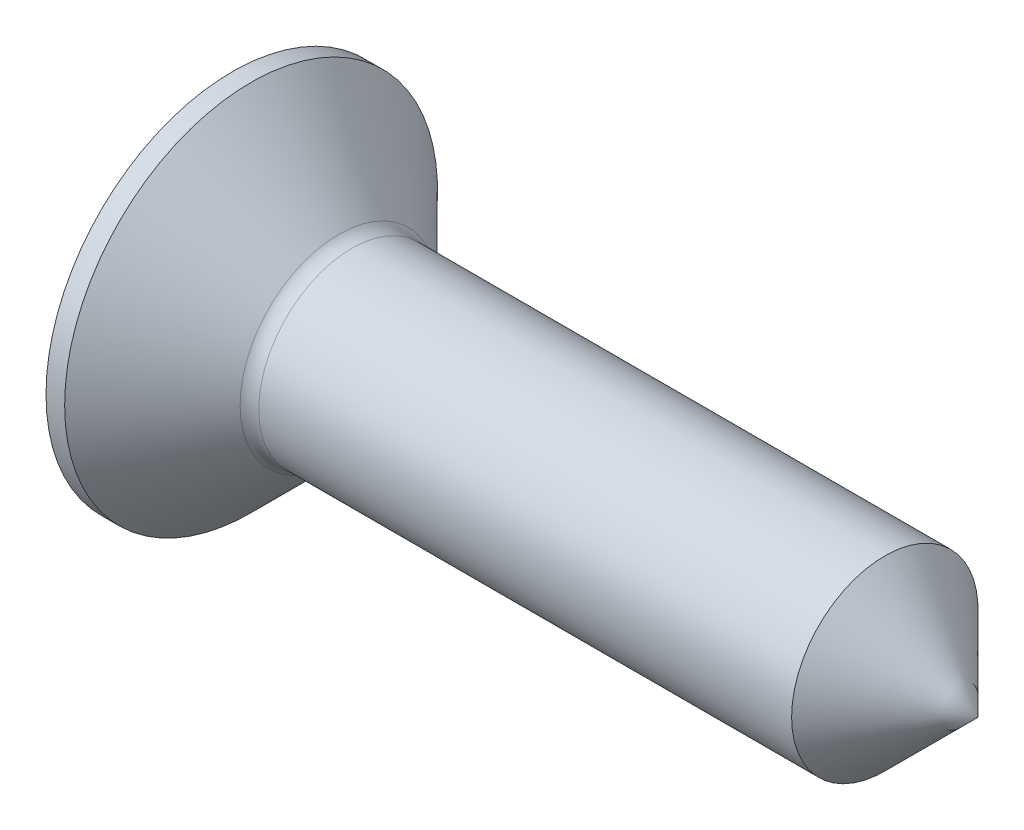
SolidWorks part; units mm, degrees
ref_plane "Front" through (0, 0, 0) normal (0, 0, 1) x (1, 0, 0)
ref_plane "Top" through (0, 0, 0) normal (0, 1, 0) x (1, 0, 0)
ref_plane "Right" through (0, 0, 0) normal (1, 0, 0) x (0, 0, -1)
sketch "Sketch1" plane through (0, 0, 0) normal (0, 1, 0) x (1, 0, 0)
  line L0 (-6.5065, 0) -> (5.6973, 0) construction
  line L1 (1.2, 1) -> (8, 1)
  line L2 (1.2, 1) -> (0.2, 2)
  line L3 (0.2, 2) -> (0, 2)
  line L4 (0, 2) -> (0, 0)
  line L5 (8, 1) -> (8, 0)
  line L6 (8, 0) -> (0, 0)
  dimension "D1" = 45
revolve "Base" add sketch "Sketch1" angle 360 about L0
cosmetic thread "ThreadCosmetic1" [suppressed] parameters "D1"=3, "D2"=1.5
sketch "Sketch3" plane through (0, 0, 0) normal (0, 0, 1) x (1, 0, 0)
  line L0 (4.8835, 0) -> (6.2249, 0) construction
  line L2 (8.1576, 0) -> (8.1576, 20)
  line L3 (8.1576, 20) -> (-12, 20)
  line L4 (-12, 20) -> (8, 0)
  line L5 (8, 0) -> (8.1576, 0)
  line L7 (8, -1) -> (8, 1) construction
  dimension "D1" = 45
  dimension "D2" = 20
  dimension "D3" = 0.1576
revolve "Cut-Revolve1" cut sketch "Sketch3" angle 360 about L0
fillet "Fillet2" radius 0.2 1 edges at (1.2, 0, 1)
ref_plane "Plane1" through (1.45, 0, 0) normal (-1, 0, 0) x (0, 0, 1)
sketch "Sketch2" plane through (0, -0.6808, 0.3068) normal (-1, 0, 0) x (0, 0, 1)
  line L0 (-2.5747, 0.6808) -> (1.9612, 0.6808) construction
  line L1 (-0.3068, 2.9897) -> (-0.3068, -1.628) construction
  line L2 (-0.5568, 0.9308) -> (-1.5568, 0.9308)
  line L3 (-0.0568, -0.5692) -> (-0.5568, -0.5692)
  line L4 (-0.0568, -0.5692) -> (-0.0568, 0.4308)
  line L5 (-0.0568, 1.9308) -> (-0.5568, 1.9308)
  line L6 (-0.5568, -0.5692) -> (-0.5568, 0.4308)
  line L7 (0.9432, 0.9308) -> (-0.0568, 0.9308)
  line L8 (0.9432, 0.9308) -> (0.9432, 0.4308)
  line L9 (0.9432, 0.4308) -> (-0.0568, 0.4308)
  line L10 (-1.5568, 0.9308) -> (-1.5568, 0.4308)
  line L11 (-0.5568, 0.4308) -> (-1.5568, 0.4308)
  line L12 (-0.5568, 0.9308) -> (-0.5568, 1.9308)
  line L13 (-0.0568, 0.9308) -> (-0.0568, 1.9308)
  point P19 (-0.5568, 0.9308)
  point P24 (-0.0568, 0.9308)
  dimension "D2" = 2.5
  dimension "D1" = 0.5
  dimension "D3" = 0.5
sketch "Sketch4" plane through (1.45, 0, 0) normal (-1, 0, 0) x (0, 0, 1)
  point P0 (0, 0)
loft "Cut-Loft1" cut profiles "Sketch2", "Sketch4"
sketch "Sketch5" plane through (0, 0, 0) normal (0, 0, 1) x (1, 0, 0)
  line L0 (4, 1.2) -> (4.25, 1.2)
  line L1 (4.25, 1.2) -> (4.25, 1)
  line L2 (4.25, 1) -> (4.125, 0.7835)
  line L3 (4, 1) -> (4.125, 0.7835)
  line L4 (4, 1.2) -> (4, 1)
  line L5 (10.7743, 0) -> (0, 0) construction
  line L6 (4, 1) -> (4.25, 1) construction
  line L7 (4.125, 1) -> (4.125, 0.7835) construction
  line L8 (7, 1) -> (1.2828, 1) construction
  point P5 (4.125, 1.2)
  dimension "D1" = 0.2
  dimension "D3" = 4
revolve "Cut-Revolve10" [suppressed] cut sketch "Sketch5" angle 360 about L5
pattern_linear "LPattern10" [suppressed] count 8 spacing 0.5 along (1, 0, 0) of bodies 105
equation "\"D2@Sketch2\" = \"m@Sketch2\""
equation "\"D3@Sketch2\" = \"D1@Sketch2\""
equation "\"D1@Sketch2\" = \"m@Sketch2\" / 5"
equation "\"D1@Plane1\" = \"k@Sketch1\" + 0.25"
equation "\"D2@Sketch5\" =  ( \"d@Sketch1\" - \"D2@ThreadCosmetic1\" )  / 2"
equation "\"D3@Sketch5\" = \"D1@ThreadCosmetic1\" + \"d@Sketch1\" / 2"
equation "\"D3@LPattern10\" =\"D2@Sketch5\"* 2"
equation "\"D1@LPattern10\" = \"D3@Sketch5\" / \"D3@LPattern10\""
